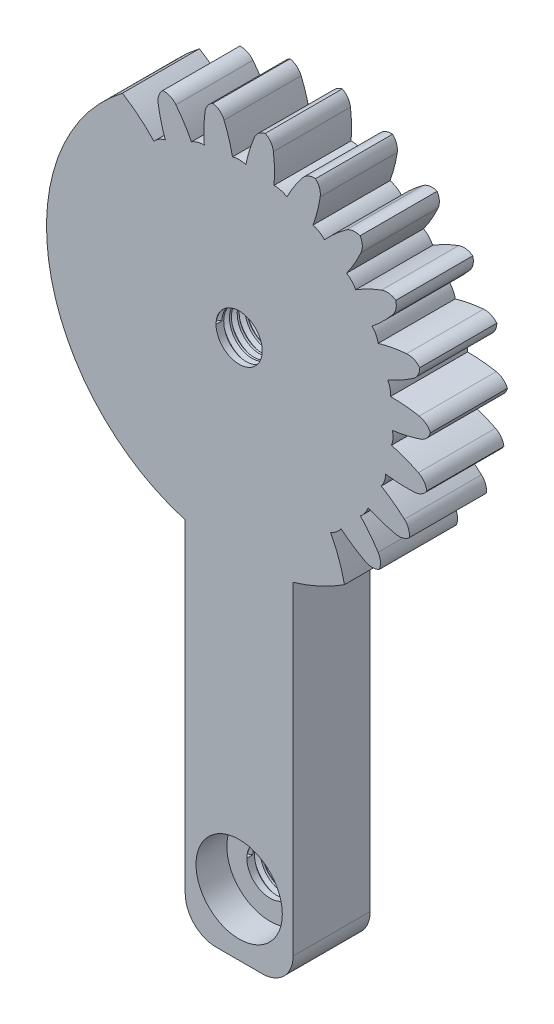
SolidWorks part; units mm, degrees
ref_plane "Front Plane" through (0, 0, 0) normal (0, 0, 1) x (1, 0, 0)
ref_plane "Top Plane" through (0, 0, 0) normal (0, 1, 0) x (1, 0, 0)
ref_plane "Right Plane" through (0, 0, 0) normal (1, 0, 0) x (0, 0, -1)
sketch "Sketch1" plane through (0, 0, 0) normal (0, 0, 1) x (1, 0, 0)
  line L4 (0, 3.4732) -> (0, -24.3817) construction
  line L5 (-3.5, -12) -> (-3.5, -35)
  line L6 (3.5, -12) -> (3.5, -35)
  line L7 (-3.5, -35) -> (3.5, -35)
  circle A0 centre (0, 0) radius 12.5
  dimension "D1" = 25
  dimension "D2" = 3.5
  dimension "D3" = 23
extrude "Boss-Extrude2" add sketch "Sketch1" along normal blind 5 contours A0 | A0 L5 L7 L6 region at (0, -23.6669, 0) region at (0, 0, 0)
sketch "Sketch3" plane through (0, 0, 5) normal (0, 0, 1) x (1, 0, 0)
  circle A0 centre (0, 0) radius 1.5
  dimension "D1" = 3
extrude "Cut-Extrude1" cut sketch "Sketch3" against normal through all
sketch "Sketch6" plane through (0, 0, 5) normal (0, 0, 1) x (1, 0, 0)
  line L0 (0, -4.0834) -> (0, 15.1037) construction
  line L1 (0, 0) -> (1.3066, 12.4315) construction
  line L2 (0, 0) -> (0.5452, 12.4881) construction
  line L3 (0, 0) -> (-0.5452, 12.4881) construction
  line L4 (0, 0) -> (-1.3066, 12.4315) construction
  arc A0 (3.5, -12) -> (-3.5, -12) centre (0, 0) ccw construction
  arc A1 (1.3066, 12.4315) -> (-1.3066, 12.4315) centre (0, 0) ccw
  arc A2 (0.4338, 9.9359) -> (-0.4338, 9.9359) centre (0, 8.5) ccw
  arc A3 (0.4338, 9.9359) -> (1.3066, 12.4315) centre (9.7504, 8.078) cw
  arc A4 (-0.4338, 9.9359) -> (-1.3066, 12.4315) centre (-9.7504, 8.078) ccw
  point P13 (0, 12.5)
  dimension "D4" = 3
  dimension "D1" = 2.5
  dimension "D2" = 6
  dimension "D3" = 4
extrude "Cut-Extrude2" cut sketch "Sketch6" against normal through all
pattern_circular "CirPattern1" count 23 over 360 about axis through (0, 0, 5) along (0, 0, -1) skipping 10, 11, 12, 13, 14, 15, 16, 17, 18, 19, 20 of "Cut-Extrude2"
fillet "Fillet1" radius 2 2 edges at (3.5, -35, 2.5) (-3.5, -35, 2.5)
sketch "Sketch14" plane through (0, 0, 5) normal (0, 0, 1) x (1, 0, 0)
  line L0 (-1.5, -35) -> (1.5, -35) construction
  circle A0 centre (0, -31) radius 2.8
  dimension "D1" = 5.6
  dimension "D2" = 4
extrude "Cut-Extrude3" cut sketch "Sketch14" against normal blind 2
sketch "Sketch15" plane through (0, 0, 3) normal (0, 0, 1) x (1, 0, 0)
  circle A0 centre (0, -31) radius 1.5
  dimension "D1" = 3
extrude "Cut-Extrude4" cut sketch "Sketch15" against normal through all
thread "Thread1" pitch 0.5 method cut profile "Thread Profile2" start angle 0, offset 0, length 10, pitch 0.5, diameter 3
ref_plane "Plane2" through (-1.5, -31, 3) normal (0, -1, 0) x (-1, 0, 0)
sketch "Thread Profile2" plane through (-1.5, -31, 3) normal (0, -1, 0) x (-1, 0, 0)
  line L0 (0, 0) -> (0, 0.5) construction
  line L1 (0, 0) -> (0.2706, 0.1562)
  line L2 (0.2706, 0.1562) -> (0.2706, 0.2187)
  line L3 (0.2706, 0.2187) -> (0, 0.375)
  line L4 (0.2706, 0.1875) -> (0, 0.1875) construction
  line L11 (0, 0) -> (0, 0.375)
  point P2 (0, 0)
  dimension "Pitch" = 0.5
  dimension "Profile_Angle" = 60
  dimension "Profile_Land" = 0.0625
  dimension "Profile_Height" = 0.2706
thread "Thread2" pitch 0.5 method cut profile "Thread Profile3" start angle 0, offset 0, length 10, pitch 0.5, diameter 3
ref_plane "Plane3" through (-1.5, 0, 5) normal (0, -1, 0) x (-1, 0, 0)
sketch "Thread Profile3" plane through (-1.5, 0, 5) normal (0, -1, 0) x (-1, 0, 0)
  line L0 (0, 0) -> (0, 0.5) construction
  line L1 (0, 0) -> (0.2706, 0.1562)
  line L2 (0.2706, 0.1562) -> (0.2706, 0.2187)
  line L3 (0.2706, 0.2187) -> (0, 0.375)
  line L4 (0.2706, 0.1875) -> (0, 0.1875) construction
  line L11 (0, 0) -> (0, 0.375)
  point P2 (0, 0)
  dimension "Pitch" = 0.5
  dimension "Profile_Angle" = 60
  dimension "Profile_Land" = 0.0625
  dimension "Profile_Height" = 0.2706
fillet "Fillet4" radius 1 22 edges at (-5.3428, 11.3006, 2.5) (-2.0958, 12.323, 2.5) (-1.3066, 12.4315, 2.5) (-4.6121, 11.618, 2.5) (2.0958, 12.323, 2.5) (1.3066, 12.4315, 2.5) (4.6121, 11.618, 2.5) (5.3428, 11.3006, 2.5) (8.1936, 9.4401, 2.5) (7.5756, 9.9428, 2.5) (9.9772, 7.5303, 2.5) (10.4366, 6.8794, 2.5) (11.6389, 4.5592, 2.5) (11.9057, 3.8085, 2.5) (12.4373, 1.25, 2.5) (12.4917, 0.4552, 2.5) (12.1513, -2.9319, 2.5) (12.3134, -2.1519, 2.5) (10.9097, -6.1016, 2.5) (11.2762, -5.3942, 2.5) (9.4027, -8.2365, 2.5) (8.8589, -8.8187, 2.5)
